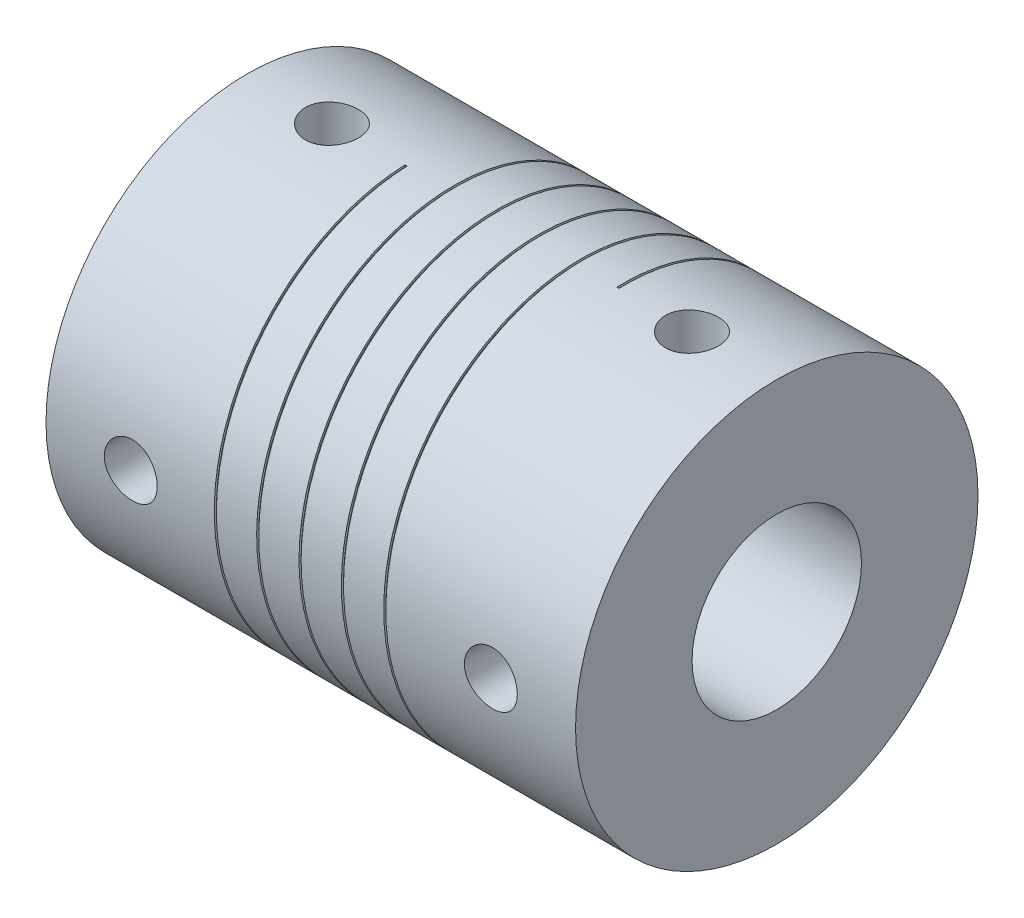
SolidWorks part; units mm, degrees
ref_plane "Front Plane" through (0, 0, 0) normal (0, 0, 1) x (1, 0, 0)
ref_plane "Top Plane" through (0, 0, 0) normal (0, 1, 0) x (1, 0, 0)
ref_plane "Right Plane" through (0, 0, 0) normal (1, 0, 0) x (0, 0, -1)
sketch "Sketch1" plane through (0, 0, 0) normal (1, 0, 0) x (0, 0, -1)
  circle A0 centre (0, 0) radius 9.5
  dimension "D1" = 19
extrude "Boss-Extrude1" add sketch "Sketch1" along normal blind 25
sketch "Sketch2" plane through (25, 0, 0) normal (1, 0, 0) x (0, 0, -1)
  circle A0 centre (0, 0) radius 4
  dimension "D1" = 8
extrude "Cut-Extrude1" cut sketch "Sketch2" against normal blind 18
sketch "Sketch3" plane through (0, 0, 0) normal (-1, 0, 0) x (0, 0, 1)
  circle A0 centre (0, 0) radius 2.5
  dimension "D1" = 5
extrude "Cut-Extrude2" cut sketch "Sketch3" against normal blind 7
sketch "Sketch4" plane through (0, 0, 0) normal (0, 0, 1) x (1, 0, 0)
  line L0 (25, 9.5) -> (0, 9.5) construction
  line L1 (7.45, 9.5) -> (7.55, 9.5)
  line L2 (7.45, 9.5) -> (7.45, 9.4)
  line L3 (7.45, 9.4) -> (7.55, 9.4)
  line L4 (7.55, 9.5) -> (7.55, 9.4)
  point P7 (7.5, 9.5)
  dimension "D1" = 0.1
  dimension "D2" = 7.5
sketch "Sketch5" plane through (7, 0, 0) normal (-1, 0, 0) x (0, 0, 1)
  circle A0 centre (0, 0) radius 9.975
  dimension "D1" = 19.95
curve "Helix/Spiral1" pitch 2 height 10 radius 9.975 centre (7, 0, 0) axis (1, 0, 0) start towards (0, 1, 0)
sweep "Cut-Sweep1" cut profiles "Sketch4" path "Helix/Spiral1" align with end faces yes
hole_wizard "M3 Tapped Hole1" positions "Sketch6" profile "Sketch7" tap size "M3" standard "DIN" end condition up to next
sketch "Sketch6" plane through (0, 0, 0) normal (0, 1, 0) x (1, 0, 0)
  line L0 (0, 9.5) -> (0, -9.5) construction
  line L1 (25, -9.5) -> (25, 9.5) construction
  point P0 (4, 0)
  point P2 (21, 0)
  dimension "D1" = 4
  dimension "D2" = 4
sketch "Sketch7" plane through (4, 0, 0) normal (1, 0, 0) x (0, 0, -1)
  line L0 (0, 0) -> (0, 9.5)
  line L1 (0, 9.5) -> (1.25, 9.5)
  line L2 (1.25, 9.5) -> (1.25, 0)
  line L5 (1.25, 0) -> (0, 0)
  line L11 (0, -6.35) -> (0, 107.95) construction
  dimension "Thru Tap Drill Dia." = 2.5
  dimension "Thru Tap Drill Depth" = 9.5
cosmetic thread "Hole Thread1" parameters "D2"=3
cosmetic thread "Hole Thread2" parameters "D2"=3
hole_wizard "M3 Tapped Hole2" positions "Sketch10" profile "Sketch9" tap size "M3" standard "DIN" end condition up to next
sketch "Sketch10" plane through (0, 0, 0) normal (0, 0, 1) x (1, 0, 0)
  line L0 (0, 9.5) -> (0, -9.5) construction
  line L1 (25, -9.5) -> (25, 9.5) construction
  point P0 (4, 0)
  point P2 (21, 0)
  dimension "D1" = 4
  dimension "D2" = 4
sketch "Sketch9" plane through (4, 0, 0) normal (1, 0, 0) x (0, 1, 0)
  line L0 (0, 0) -> (0, 9.5)
  line L1 (0, 9.5) -> (1.25, 9.5)
  line L2 (1.25, 9.5) -> (1.25, 0)
  line L5 (1.25, 0) -> (0, 0)
  line L11 (0, -6.35) -> (0, 107.95) construction
  dimension "Thru Tap Drill Dia." = 2.5
  dimension "Thru Tap Drill Depth" = 9.5
cosmetic thread "Hole Thread3" parameters "D2"=3
cosmetic thread "Hole Thread4" parameters "D2"=3
